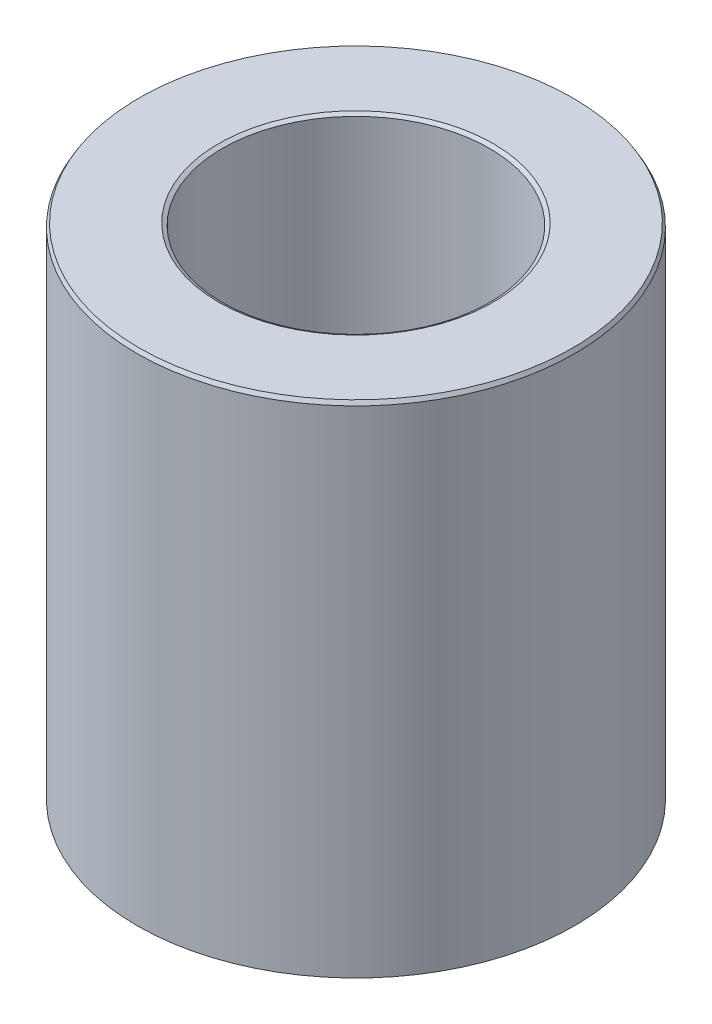
SolidWorks part; units mm, degrees
ref_plane "Front Plane" through (0, 0, 0) normal (0, 0, 1) x (1, 0, 0)
ref_plane "Top Plane" through (0, 0, 0) normal (0, 1, 0) x (1, 0, 0)
ref_plane "Right Plane" through (0, 0, 0) normal (1, 0, 0) x (0, 0, -1)
sketch "Sketch1" plane through (0, 0, 0) normal (0, 1, 0) x (1, 0, 0)
  circle A0 centre (0, 0) radius 42.5
  dimension "SLEEVE_OD" = 85
extrude "Boss-Extrude1" add sketch "Sketch1" along normal blind 97.3661
sketch "Sketch2" plane through (0, 0, 0) normal (0, 1, 0) x (1, 0, 0)
  circle A0 centre (0, 0) radius 25.938
  dimension "BORE_D" = 51.876
extrude "Cut-Extrude1" cut sketch "Sketch2" along normal through all
chamfer "Chamfer1" distance 0.731 angle 30 4 edges at (0, 97.3661, 25.938) (0, 0, 25.938) (0, 0, 42.5) (0, 97.3661, 42.5) first distance on face at (0, 97.3661, 25.938) first distance on face at (0, 0, 25.938) first distance on face at (0, 97.3661, 42.5)
